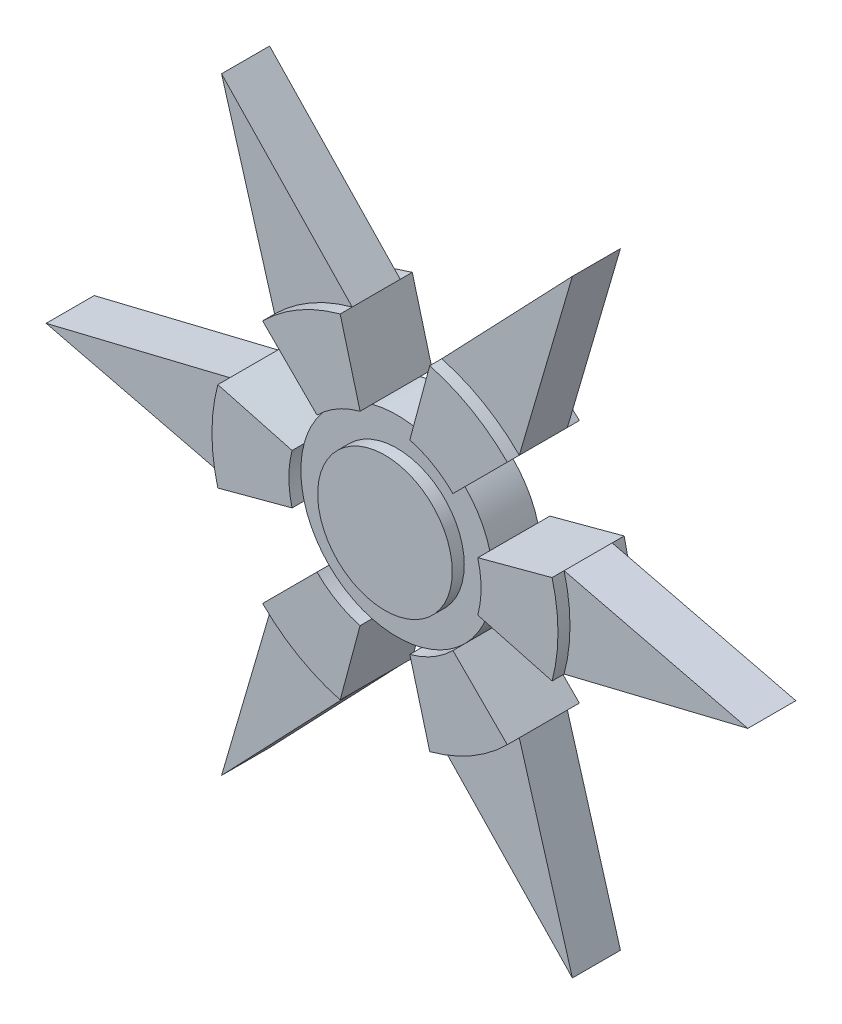
SolidWorks part; units mm, degrees
ref_plane "Front Plane" through (0, 0, 0) normal (0, 0, 1) x (1, 0, 0)
ref_plane "Top Plane" through (0, 0, 0) normal (0, 1, 0) x (1, 0, 0)
ref_plane "Right Plane" through (0, 0, 0) normal (1, 0, 0) x (0, 0, -1)
sketch "Sketch1" plane through (0, 0, 0) normal (0, 0, 1) x (1, 0, 0)
  line L0 (0, 0) -> (0, -12315.396) construction
  line L1 (0, 0) -> (12315.396, 0) construction
  line L2 (34.7733, 9.3175) -> (19.3185, 5.1764)
  line L3 (34.7733, -9.3175) -> (19.3185, -5.1764)
  line L4 (25.4558, -25.4558) -> (14.1421, -14.1421)
  line L5 (9.3175, -34.7733) -> (5.1764, -19.3185)
  line L6 (-9.3175, -34.7733) -> (-5.1764, -19.3185)
  line L7 (-25.4558, -25.4558) -> (-14.1421, -14.1421)
  line L8 (-34.7733, -9.3175) -> (-19.3185, -5.1764)
  line L9 (-34.7733, 9.3175) -> (-19.3185, 5.1764)
  line L10 (-25.4558, 25.4558) -> (-14.1421, 14.1421)
  line L11 (-9.3175, 34.7733) -> (-5.1764, 19.3185)
  line L12 (9.3175, 34.7733) -> (5.1764, 19.3185)
  line L13 (25.4558, 25.4558) -> (14.1421, 14.1421)
  line L14 (34.7733, 9.3175) -> (73, 0)
  line L15 (34.7733, -9.3175) -> (73, 0)
  line L16 (25.4558, -25.4558) -> (36.5, -63.2199)
  line L17 (9.3175, -34.7733) -> (36.5, -63.2199)
  line L18 (-9.3175, -34.7733) -> (-36.5, -63.2199)
  line L19 (-25.4558, -25.4558) -> (-36.5, -63.2199)
  line L20 (-34.7733, -9.3175) -> (-73, 0)
  line L21 (-34.7733, 9.3175) -> (-73, 0)
  line L22 (-25.4558, 25.4558) -> (-36.5, 63.2199)
  line L23 (-9.3175, 34.7733) -> (-36.5, 63.2199)
  line L24 (9.3175, 34.7733) -> (36.5, 63.2199)
  line L25 (25.4558, 25.4558) -> (36.5, 63.2199)
  circle A0 centre (0, 0) radius 14
  circle A1 centre (0, 0) radius 20
  circle A2 centre (0, 0) radius 36
  circle A3 centre (0, 0) radius 73 construction
  point P37 (0, 0)
  point P53 (0, 0)
  dimension "D1" = 28
  dimension "D2" = 40
  dimension "D3" = 72
  dimension "D4" = 146
  dimension "D5" = 30
  dimension "D7" = 6
  dimension "D6" = 6
extrude "Boss-Extrude1" add sketch "Sketch1" along normal mid plane 15 contours A0 | L11 A2 L10 A1 | L13 A2 L12 A1 | L9 A2 L8 A1 | L3 A2 L2 A1 | L5 A2 L4 A1 | L7 A2 L6 A1 region at (28.4345, 0, 0) region at (14.2172, 24.625, 0) region at (14.2172, -24.625, 0) region at (-14.2172, 24.625, 0) region at (-14.2172, -24.625, 0) region at (-28.4345, 0, 0) region at (0, 0, 0)
extrude "Boss-Extrude2" add sketch "Sketch1<3>" along normal mid plane 10 contours A2 L23 L22 | A2 L25 L24 | A2 L15 L14 | A2 L21 L20 | A2 L19 L18 | A2 L17 L16 | A1 A0 region at (48.0651, 0, 0) region at (19.2681, 2.5367, 0) region at (24.0326, 41.6256, 0) region at (24.0326, -41.6256, 0) region at (-24.0326, 41.6256, 0) region at (-24.0326, -41.6256, 0) region at (-48.0651, 0, 0)
sketch "Sketch1<3>" plane through (0, 0, 0) normal (0, 0, 1) x (1, 0, 0) same geometry as "Sketch1"
